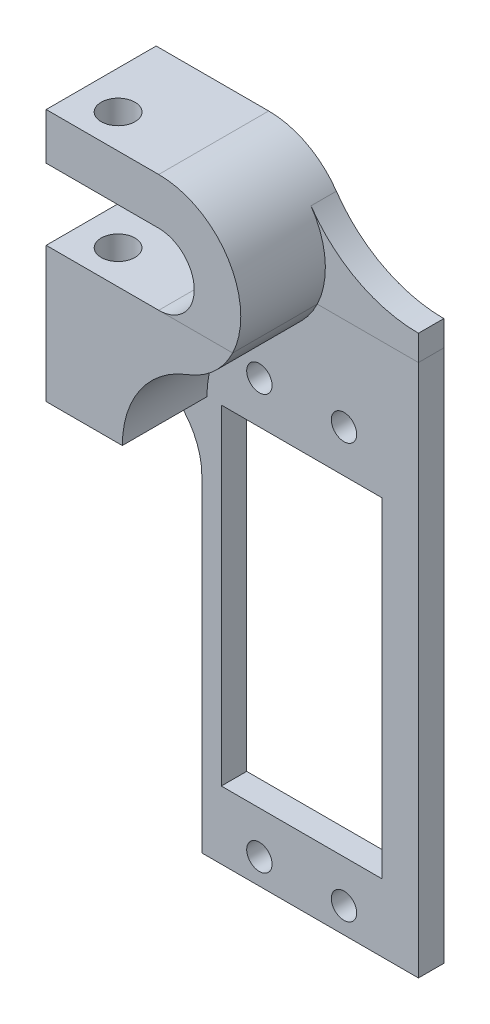
SolidWorks part; units mm, degrees
ref_plane "Спереди" through (0, 0, 0) normal (0, 0, 1) x (1, 0, 0)
ref_plane "Сверху" through (0, 0, 0) normal (0, 1, 0) x (1, 0, 0)
ref_plane "Справа" through (0, 0, 0) normal (1, 0, 0) x (0, 0, -1)
sketch "Эскиз1" plane through (0, 0, 0) normal (0, 0, 1) x (1, 0, 0)
  line L0 (-20.2, 19.5) -> (-20.2, 35.5)
  line L1 (-9.5, 19.5) -> (9.5, 19.5)
  line L2 (-9.5, 19.5) -> (-9.5, -19.5)
  line L3 (-9.5, -19.5) -> (9.5, -19.5)
  line L4 (9.5, 19.5) -> (9.5, -19.5)
  line L5 (-9.5, 19.5) -> (9.5, -19.5) construction
  line L6 (-9.5, -19.5) -> (9.5, 19.5) construction
  line L8 (-11.8, 11.1) -> (-11.8, -27.5)
  line L9 (-11.8, -27.5) -> (13.8, -27.5)
  line L10 (13.8, 38.5) -> (13.8, -27.5)
  line L11 (-5, 24.5) -> (5, 24.5) construction
  line L12 (-5, 24.5) -> (-5, -24.5) construction
  line L13 (-5, -24.5) -> (5, -24.5) construction
  line L14 (5, 24.5) -> (5, -24.5) construction
  line L15 (-5, 24.5) -> (5, -24.5) construction
  line L16 (-5, -24.5) -> (5, 24.5) construction
  line L17 (-20.2, 35.5) -> (-6.9, 35.5)
  line L18 (-20.2, 43.9) -> (-6.9, 43.9)
  line L19 (-20.2, 43.9) -> (-20.2, 49.4)
  line L20 (-20.2, 49.4) -> (-6.9, 49.4)
  circle A0 centre (-5, 24.5) radius 1.5
  circle A1 centre (5, 24.5) radius 1.5
  circle A2 centre (-5, -24.5) radius 1.5
  circle A3 centre (5, -24.5) radius 1.5
  arc A4 (-11.8, 11.1) -> (-20.2, 19.5) centre (-20.2, 11.1) ccw
  arc A6 (-6.9, 35.5) -> (-6.9, 43.9) centre (-6.9, 39.7) ccw
  arc A7 (1.0978, 45.1886) -> (-6.9, 49.4) centre (-6.9, 39.7) ccw
  arc A8 (1.0978, 45.1886) -> (13.8, 38.5) centre (13.8, 53.9055) ccw
  point P0 (0, 0)
  point P5 (0, 0)
  point P12 (0, 0)
  dimension "D8" = 3
  dimension "D10" = 39
  dimension "D11" = 34
  dimension "D13" = 8.4
  dimension "D15" = 13.3
  dimension "D1" = 39
  dimension "D2" = 19
  dimension "D3" = 8
  dimension "D4" = 2.3
  dimension "D5" = 4.3
  dimension "D6" = 49
  dimension "D7" = 10
  dimension "D9" = 66
  dimension "D12" = 16
  dimension "D14" = 5.5
extrude "Основа" add sketch "Эскиз1" along normal blind 3
sketch "Эскиз2" plane through (0, 0, 3) normal (0, 0, 1) x (1, 0, 0)
  line L0 (-20.2, 19.5) -> (-20.2, 35.5)
  line L1 (-20.2, 35.5) -> (-6.9, 35.5)
  line L2 (-6.9, 43.9) -> (-20.2, 43.9)
  line L3 (-20.2, 43.9) -> (-20.2, 49.4)
  line L4 (-20.2, 49.4) -> (-6.9, 49.4)
  line L5 (-20.2, 19.5) -> (-11.2, 19.5)
  arc A0 (-6.9, 35.5) -> (-6.9, 43.9) centre (-6.9, 39.7) ccw construction
  arc A1 (-6.9, 43.9) -> (-6.9, 35.5) centre (-6.9, 39.7) cw
  arc A2 (-3.4949, 30.6173) -> (-6.9, 49.4) centre (-6.9, 39.7) ccw
  arc A4 (1.0978, 45.1886) -> (-6.9, 49.4) centre (-6.9, 39.7) ccw construction
  arc A6 (-3.4949, 30.6173) -> (-11.2, 19.5) centre (0.6729, 19.5) ccw
  dimension "D1" = 9
extrude "Крюк" add sketch "Эскиз2" along normal blind 10
sketch "Эскиз3" plane through (0, 19.5, 0) normal (0, -1, 0) x (1, 0, 0)
  line L0 (-20.2, 13) -> (-11.2, 13) construction
  circle A0 centre (-15.7, 9) radius 2
  point P5 (-15.7, 13)
  dimension "D1" = 4
  dimension "D2" = 4
extrude "Вырез под толкатель" cut sketch "Эскиз3" against normal up to surface (29.9 mm away) up to face at (-13.55, 49.4, 6.5)
split "Разделить1" bodies to split 105 resulting bodies 106 107 split by face at (-15.7, 35.5, 7)
